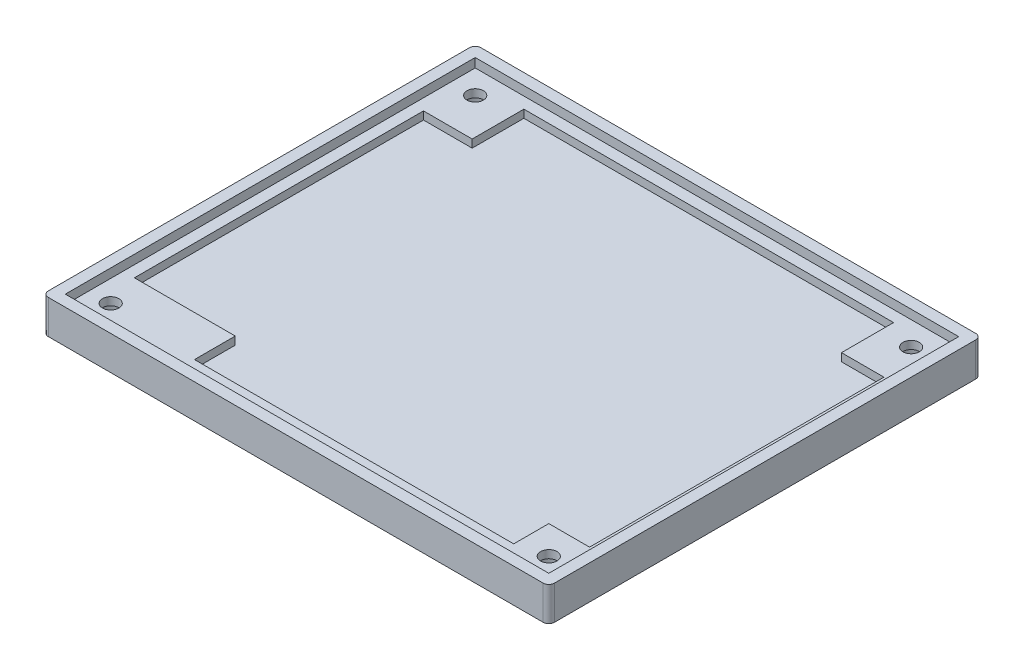
SolidWorks part; units mm, degrees
ref_plane "Front Plane" through (0, 0, 0) normal (0, 0, 1) x (1, 0, 0)
ref_plane "Top Plane" through (0, 0, 0) normal (0, 1, 0) x (1, 0, 0)
ref_plane "Right Plane" through (0, 0, 0) normal (1, 0, 0) x (0, 0, -1)
sketch "Sketch1" plane through (0, 0, 0) normal (0, 1, 0) x (1, 0, 0)
  line L0 (-47.7758, -21.4957) -> (-65.5905, -21.4957)
  line L1 (-67.5905, 40.7043) -> (17.8095, 40.7043)
  line L2 (-67.5905, 40.7043) -> (-67.5905, -31.6957)
  line L3 (-67.5905, -31.6957) -> (17.8095, -31.6957)
  line L4 (17.8095, 40.7043) -> (17.8095, -31.6957)
  line L5 (-69.5905, 42.7043) -> (19.8095, 42.7043)
  line L6 (-69.5905, 42.7043) -> (-69.5905, -33.6957)
  line L7 (-69.5905, -33.6957) -> (19.8095, -33.6957)
  line L8 (19.8095, 42.7043) -> (19.8095, -33.6957)
  line L9 (-56.9905, 29.5682) -> (-56.9905, 38.7043)
  line L12 (-56.9905, 38.7043) -> (8.3095, 38.7043)
  line L14 (-65.5905, -21.4957) -> (-65.5905, 29.5682)
  line L15 (-65.5905, 29.5682) -> (-56.9905, 29.5682)
  line L17 (8.3095, 38.7043) -> (8.3095, 29.5043)
  line L18 (8.3095, 29.5043) -> (15.8095, 29.5043)
  line L30 (-69.5905, 42.7043) -> (-69.5905, 27.3682)
  line L34 (-69.5905, -33.6957) -> (-69.5905, -42.0318)
  line L39 (15.8095, 29.5043) -> (15.8095, -22.4957)
  line L40 (15.8095, -22.4957) -> (8.6095, -22.4957)
  line L41 (8.6095, -22.4957) -> (8.6095, -28.6957)
  line L42 (8.6095, -28.6957) -> (-47.7758, -28.6957)
  line L43 (-47.7758, -28.6957) -> (-47.7758, -21.4957)
  circle A0 centre (13.6095, 36.5043) radius 1.45
  circle A1 centre (-63.7758, -27.4957) radius 1.45
  circle A7 centre (-63.3905, 36.5043) radius 1.45
  circle A8 centre (13.6095, -27.4957) radius 1.45
  dimension "D7" = 2.9
  dimension "D10" = 2.9
  dimension "D45" = 2.9
  dimension "D46" = 2.9
  dimension "D1" = 85.4
  dimension "D2" = 72.4
  dimension "D3" = 2
  dimension "D5" = 2
  dimension "D8" = 2
  dimension "D9" = 4.2
  dimension "D11" = 6.9361
  dimension "D12" = 4.2
  dimension "D13" = 6
  dimension "D14" = 6.4
  dimension "D17" = 2
  dimension "D18" = 2
  dimension "D20" = 2
  dimension "D22" = 5.3
  dimension "D23" = 7
  dimension "D25" = 2
  dimension "D47" = 4.2
  dimension "D48" = 4.2
  dimension "D49" = 4.2
  dimension "D50" = 4.2
  dimension "D52" = 5
  dimension "D53" = 5
  dimension "D56" = 3
  dimension "D57" = 16
  dimension "D62" = 4.2
extrude "Boss-Extrude1" add sketch "Sketch1" against normal blind 6 contours L6 | L6 | L8 | L8 | L5 L8 L7 L6 region at (-24.8905, 0, -41.5283)
extrude "Cut-Extrude2" cut sketch "Sketch1<5>" against normal blind 1.6 contours L1 L4 L3 L2
sketch "Sketch1<5>" plane through (0, 0, 0) normal (0, 1, 0) x (1, 0, 0) same geometry as "Sketch1"
extrude "Cut-Extrude3" cut sketch "Sketch1<6>" against normal blind 3 contours L15 L9 L12 L17 L18 L39 L40 L41 L42 L43 L0 L14
sketch "Sketch1<6>" plane through (0, 0, 0) normal (0, 1, 0) x (1, 0, 0) same geometry as "Sketch1"
extrude "Cut-Extrude4" cut sketch "Sketch1<7>" against normal through all contours A0 | A1 | A7 | A8
sketch "Sketch1<7>" plane through (0, 0, 0) normal (0, 1, 0) x (1, 0, 0) same geometry as "Sketch1"
fillet "Fillet1" radius 1 4 edges at (-69.5905, -3, 33.6957) (-69.5905, -3, -42.7043) (19.8095, -3, 33.6957) (19.8095, -3, -42.7043)
sketch "Sketch2" plane through (0, -6, 0) normal (0, -1, 0) x (1, 0, 0)
  circle A0 centre (-63.7758, 27.4957) radius 3.5
  circle A1 centre (13.6095, 27.4957) radius 3.5
  circle A2 centre (13.6095, -36.5043) radius 3.5
  circle A3 centre (-63.3905, -36.5043) radius 3.5
  dimension "D1" = 7
  dimension "D2" = 7
  dimension "D3" = 7
  dimension "D4" = 7
extrude "Cut-Extrude5" cut sketch "Sketch2" against normal blind 3
fillet "Fillet2" [suppressed] radius 1
